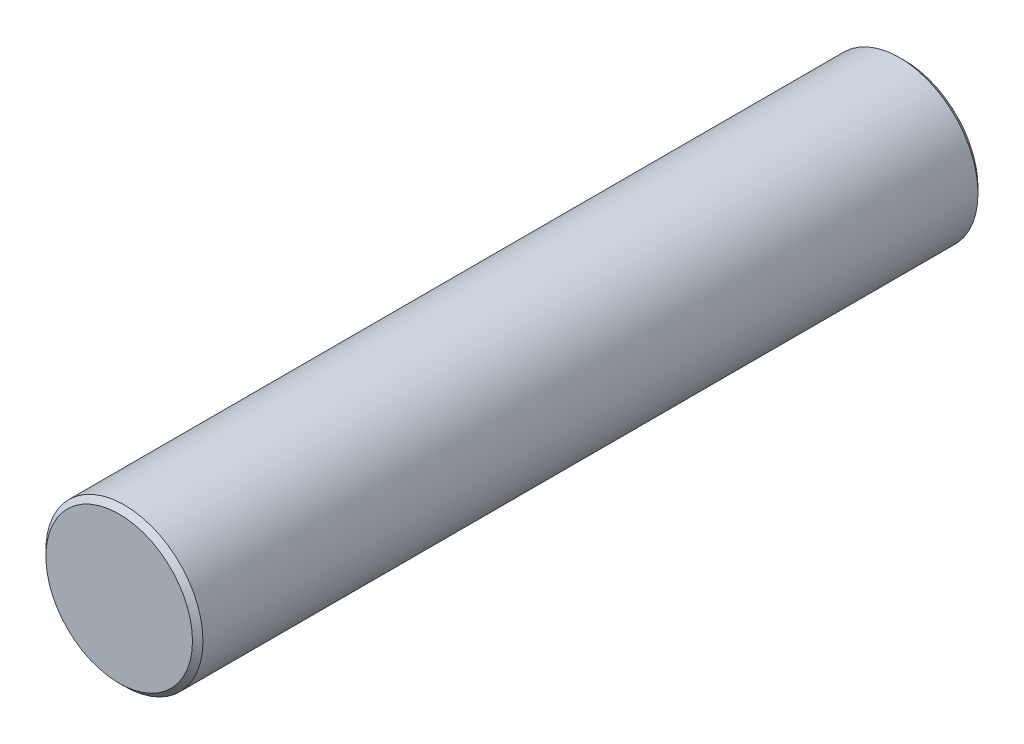
SolidWorks part; units mm, degrees
material "ASTM A36 Steel"
ref_plane "Front Plane" through (0, 0, 0) normal (0, 0, 1) x (1, 0, 0)
ref_plane "Top Plane" through (0, 0, 0) normal (0, 1, 0) x (1, 0, 0)
ref_plane "Right Plane" through (0, 0, 0) normal (1, 0, 0) x (0, 0, -1)
sketch "Sketch1" plane through (0, 0, 0) normal (0, 0, 1) x (1, 0, 0)
  circle A0 centre (0, 0) radius 30
  dimension "D1" = 60
extrude "Boss-Extrude1" add sketch "Sketch1" along normal blind 300
chamfer "Chamfer1" distance 2 angle 45 2 edges at (30, 0, 300) (30, 0, 0)
sketch "Sketch2" plane through (0, 0, 0) normal (0, 0, -1) x (-1, 0, 0)
  circle A0 centre (0, 0) radius 5
  dimension "D1" = 10
extrude "Cut-Extrude1" cut sketch "Sketch2" against normal blind 30
thread "Thread1" pitch 1.5 method extrude profile "Thread Profile1" start angle 0, offset 0, length 30, pitch 1.5, diameter 10
ref_plane "Plane1" through (5, 0, 0) normal (0, -1, 0) x (1, 0, 0)
sketch "Thread Profile1" plane through (5, 0, 0) normal (0, -1, 0) x (1, 0, 0)
  line L0 (0, 0) -> (0, 1.5) construction
  line L1 (0, 1.125) -> (-0.8119, 0.6563)
  line L2 (-0.8119, 0.6563) -> (-0.8119, 0.4688)
  line L3 (-0.8119, 0.4688) -> (0, 0)
  line L4 (-0.8119, 0.5625) -> (0, 0.5625) construction
  line L11 (0, 1.125) -> (0, 0)
  point P6 (0, 0)
  dimension "Pitch" = 1.5
  dimension "Profile_Angle" = 60
  dimension "Profile_Land" = 0.1875
  dimension "Profile_Height" = 0.8119
